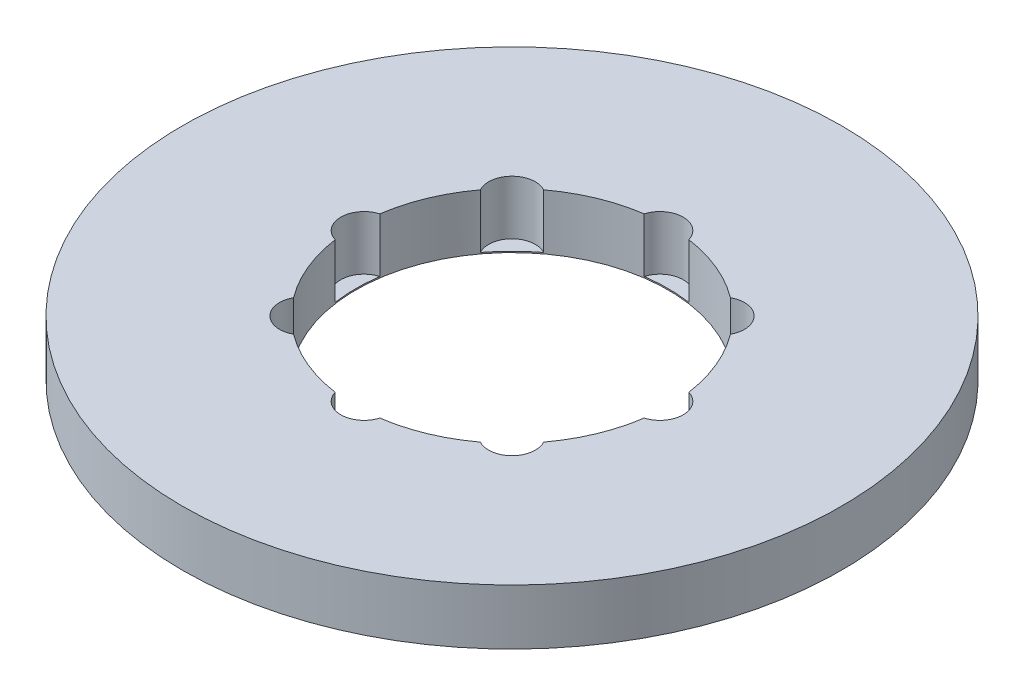
SolidWorks part; units mm, degrees
ref_plane "Front Plane" through (0, 0, 0) normal (0, 0, 1) x (1, 0, 0)
ref_plane "Top Plane" through (0, 0, 0) normal (0, 1, 0) x (1, 0, 0)
ref_plane "Right Plane" through (0, 0, 0) normal (1, 0, 0) x (0, 0, -1)
sketch "Sketch1" plane through (0, 0, 0) normal (0, 1, 0) x (1, 0, 0)
  circle A0 centre (0, 0) radius 95
  dimension "FLANGE_OD" = 190
extrude "Boss-Extrude1" add sketch "Sketch1" along normal blind 16
sketch "Sketch2" plane through (0, 0, 0) normal (0, 1, 0) x (1, 0, 0)
  circle A0 centre (0, 0) radius 45
  dimension "BORE_D" = 90
extrude "Cut-Extrude1" cut sketch "Sketch2" along normal through all
sketch "Sketch3" plane through (0, 16, 0) normal (0, 1, 0) x (1, 0, 0)
  circle A0 centre (0, 0) radius 42.6381 construction
  circle A1 centre (-42.6381, 0) radius 6.7155
  dimension "BOLT_D" = 13.431
  dimension "BOLT_PCD" = 85.2762
extrude "Cut-Extrude2" cut sketch "Sketch3" against normal blind 15.6329
pattern_circular "CirPattern1" count 8 over 360 about axis through (0, 0, 0) along (0, 1, 0) of "Cut-Extrude2"
